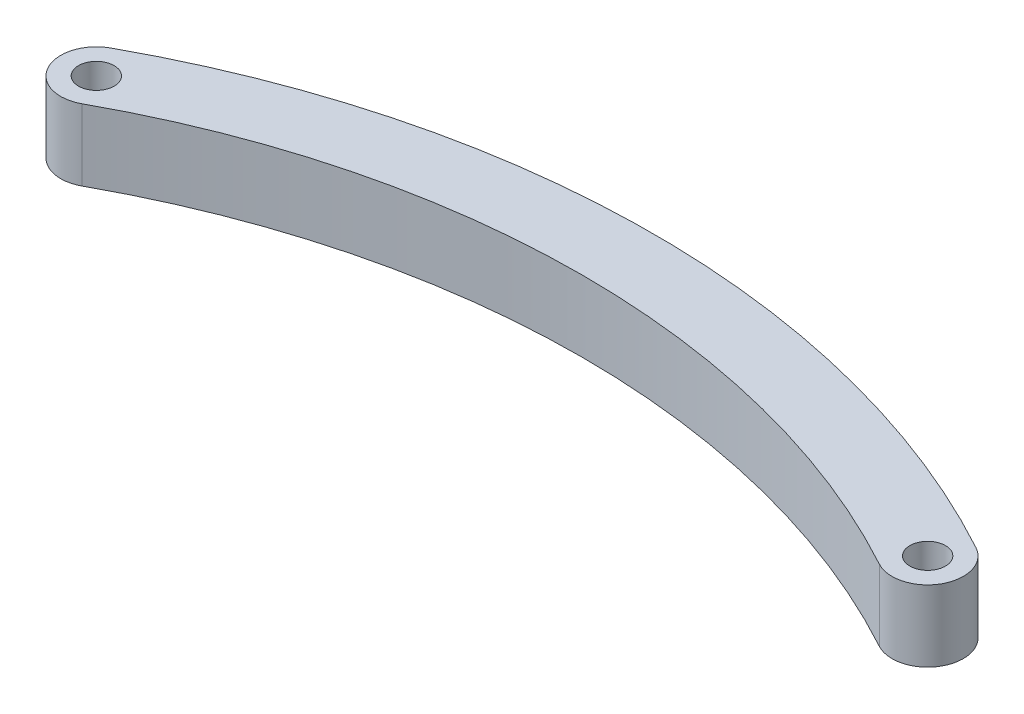
SolidWorks part; units mm, degrees
ref_plane "Front Plane" through (0, 0, 0) normal (0, 0, 1) x (1, 0, 0)
ref_plane "Top Plane" through (0, 0, 0) normal (0, 1, 0) x (1, 0, 0)
ref_plane "Right Plane" through (0, 0, 0) normal (1, 0, 0) x (0, 0, -1)
sketch "Esquisse1" plane through (0, 0, 0) normal (0, 1, 0) x (1, 0, 0)
  line L0 (-35, 0) -> (0, 0) construction
  line L1 (0, 0) -> (35, 0) construction
  circle A0 centre (-35, 0) radius 1.5
  circle A1 centre (35, 0) radius 1.5
  circle A2 centre (-35, 0) radius 3
  circle A3 centre (35, 0) radius 3
  circle A4 centre (0, -64.0625) radius 70
  circle A5 centre (0, -64.0625) radius 76
  dimension "D2" = 3
  dimension "D3" = 6
  dimension "D4" = 140
  dimension "D5" = 152
  dimension "D1" = 35
extrude "Boss.-Extru.1" add sketch "Esquisse1" along normal blind 6 contours A3 A5 A2 A4 | A2 A0 | A3 A1 region at (-32.4928, 0, 1.4872) region at (0, 0, -6.3427) region at (37.5072, 0, -1.4872)
